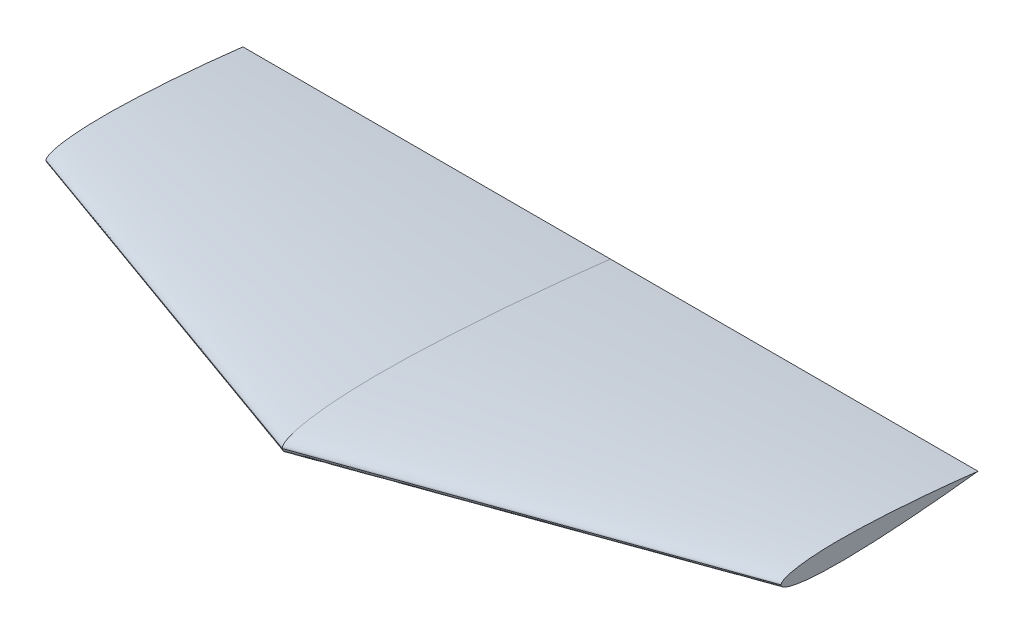
SolidWorks part; units mm, degrees
ref_plane "Front Plane" through (0, 0, 0) normal (0, 0, 1) x (1, 0, 0)
ref_plane "Top Plane" through (0, 0, 0) normal (0, 1, 0) x (1, 0, 0)
ref_plane "Right Plane" through (0, 0, 0) normal (1, 0, 0) x (0, 0, -1)
sketch "Sketch3" plane through (0, 0, 0) normal (1, 0, 0) x (0, 0, -1)
  line L0 (0, 0) -> (-250, 0) construction
  spline S0 degree 4 poles (-250, 0) (-249.9999, 0.1958) (-249.9612, 0.6039) (-249.7596, 1.2633) (-249.1282, 2.2398) (-248.1098, 3.1752) (-246.5761, 4.1828) (-244.1271, 5.3667) (-240.0739, 6.8179) (-232.84, 8.6113) (-221.2945, 10.4497) (-205.8077, 11.8178) (-187.4923, 12.5325) (-167.6157, 12.5624) (-147.9613, 12.1042) (-127.9831, 11.2209) (-108.5655, 10.1073) (-88.2725, 8.6479) (-69.4578, 7.1641) (-48.2492, 5.205) (-31.0441, 3.5474) (-5.6278, 0.7144) (5.3818, -0.6305) (19.3913, -2.4508) (24.9342, -3.2323) knots 0 0 0 0 0 0.002791 0.005883 0.009735 0.016522 0.022438 0.032158 0.048634 0.078249 0.129037 0.199997 0.270957 0.341918 0.412878 0.483838 0.554798 0.625759 0.696719 0.767679 0.83864 0.9096 1 1 1 1 1 construction
  spline S1 degree 4 poles (-250, 0) (-249.9999, 0.1958) (-249.9612, 0.6039) (-249.7596, 1.2633) (-249.1282, 2.2398) (-248.1098, 3.1752) (-246.5761, 4.1828) (-244.1271, 5.3667) (-240.0739, 6.8179) (-232.84, 8.6113) (-221.2945, 10.4497) (-205.8077, 11.8178) (-187.4923, 12.5325) (-167.6157, 12.5624) (-147.9613, 12.1042) (-127.9831, 11.2209) (-108.5655, 10.1073) (-88.2725, 8.6479) (-69.4578, 7.1641) (-48.2492, 5.205) (-31.0441, 3.5474) (-13.2038, 1.5588) (-4.4672, 0.5411) (0, 0) knots 0 0 0 0 0 0.002791 0.005883 0.009735 0.016522 0.022438 0.032158 0.048634 0.078249 0.129037 0.199997 0.270957 0.341918 0.412878 0.483838 0.554798 0.625759 0.696719 0.767679 0.83864 0.9096 0.9096 0.9096 0.9096 0.9096
  spline S2 degree 4 poles (-250, 0) (-249.9999, -0.1958) (-249.9612, -0.6039) (-249.7596, -1.2633) (-249.1282, -2.2398) (-248.1098, -3.1752) (-246.5761, -4.1828) (-244.1271, -5.3667) (-240.0739, -6.8179) (-232.84, -8.6113) (-221.2945, -10.4497) (-205.8077, -11.8178) (-187.4923, -12.5325) (-167.6157, -12.5624) (-147.9613, -12.1042) (-127.9831, -11.2209) (-108.5655, -10.1073) (-88.2725, -8.6479) (-69.4578, -7.1641) (-48.2492, -5.205) (-31.0441, -3.5474) (-13.2038, -1.5588) (-4.4672, -0.5411) (0, 0) knots 0 0 0 0 0 0.002791 0.005883 0.009735 0.016522 0.022438 0.032158 0.048634 0.078249 0.129037 0.199997 0.270957 0.341918 0.412878 0.483838 0.554798 0.625759 0.696719 0.767679 0.83864 0.9096 0.9096 0.9096 0.9096 0.9096
  point P0 (0, 0)
ref_plane "Plane1" through (280, 0, 0) normal (1, 0, 0) x (0, 0, -1)
sketch "Sketch4" plane through (280, 0, 0) normal (1, 0, 0) x (0, 0, -1)
  line L0 (0, 0) -> (-150, 0) construction
  spline S0 degree 4 poles (-150, 0) (-149.9999, 0.1175) (-149.9767, 0.3624) (-149.8557, 0.758) (-149.4769, 1.3439) (-148.8659, 1.9051) (-147.9457, 2.5097) (-146.4763, 3.22) (-144.0443, 4.0908) (-139.704, 5.1668) (-132.7767, 6.2698) (-123.4846, 7.0907) (-112.4954, 7.5195) (-100.5694, 7.5374) (-88.7768, 7.2625) (-76.7899, 6.7325) (-65.1393, 6.0644) (-52.9635, 5.1887) (-41.6747, 4.2985) (-28.9495, 3.123) (-18.6265, 2.1284) (-3.3767, 0.4286) (3.2291, -0.3783) (11.6348, -1.4705) (14.9605, -1.9394) knots 0 0 0 0 0 0.002791 0.005883 0.009735 0.016522 0.022438 0.032158 0.048634 0.078249 0.129037 0.199997 0.270957 0.341918 0.412878 0.483838 0.554798 0.625759 0.696719 0.767679 0.83864 0.9096 1 1 1 1 1 construction
  spline S1 degree 4 poles (-150, 0) (-149.9999, 0.1175) (-149.9767, 0.3624) (-149.8557, 0.758) (-149.4769, 1.3439) (-148.8659, 1.9051) (-147.9457, 2.5097) (-146.4763, 3.22) (-144.0443, 4.0908) (-139.704, 5.1668) (-132.7767, 6.2698) (-123.4846, 7.0907) (-112.4954, 7.5195) (-100.5694, 7.5374) (-88.7768, 7.2625) (-76.7899, 6.7325) (-65.1393, 6.0644) (-52.9635, 5.1887) (-41.6747, 4.2985) (-28.9495, 3.123) (-18.6265, 2.1284) (-7.9223, 0.9353) (-2.6803, 0.3247) (0, 0) knots 0 0 0 0 0 0.002791 0.005883 0.009735 0.016522 0.022438 0.032158 0.048634 0.078249 0.129037 0.199997 0.270957 0.341918 0.412878 0.483838 0.554798 0.625759 0.696719 0.767679 0.83864 0.9096 0.9096 0.9096 0.9096 0.9096
  spline S2 degree 4 poles (-150, 0) (-149.9999, -0.1175) (-149.9767, -0.3624) (-149.8557, -0.758) (-149.4769, -1.3439) (-148.8659, -1.9051) (-147.9457, -2.5097) (-146.4763, -3.22) (-144.0443, -4.0908) (-139.704, -5.1668) (-132.7767, -6.2698) (-123.4846, -7.0907) (-112.4954, -7.5195) (-100.5694, -7.5374) (-88.7768, -7.2625) (-76.7899, -6.7325) (-65.1393, -6.0644) (-52.9635, -5.1887) (-41.6747, -4.2985) (-28.9495, -3.123) (-18.6265, -2.1284) (-7.9223, -0.9353) (-2.6803, -0.3247) (0, 0) knots 0 0 0 0 0 0.002791 0.005883 0.009735 0.016522 0.022438 0.032158 0.048634 0.078249 0.129037 0.199997 0.270957 0.341918 0.412878 0.483838 0.554798 0.625759 0.696719 0.767679 0.83864 0.9096 0.9096 0.9096 0.9096 0.9096
loft "Loft1" add profiles "Sketch3", "Sketch4" connector at (0, 0, 0) connector at (280, 0, 0)
mirror "Mirror1" about plane through (0, -11.0805, 126.3057) normal (-1, 0, 0) of "Loft1"
